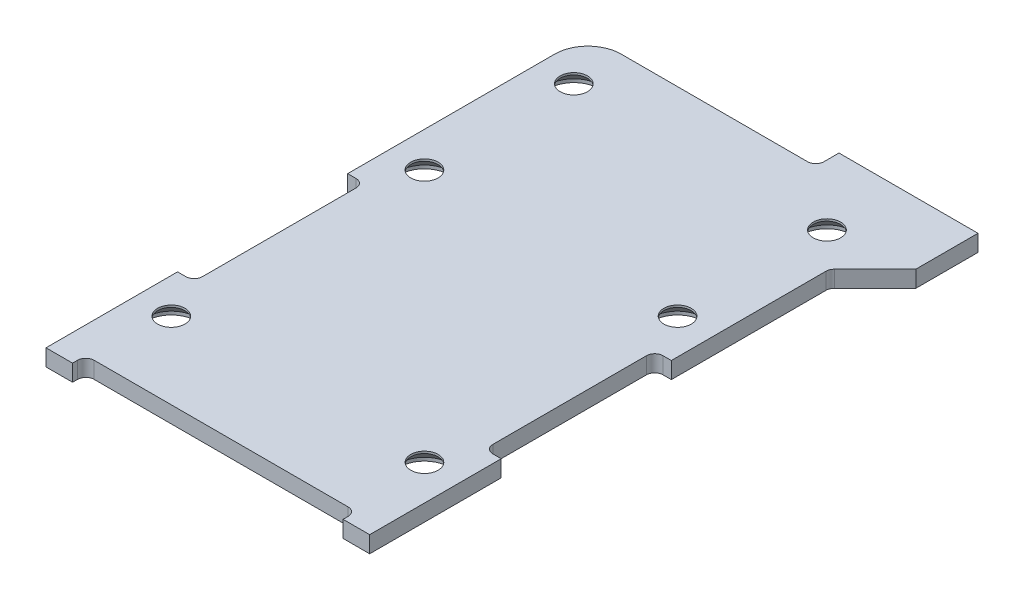
SolidWorks part; units mm, degrees
ref_plane "Front Plane" through (0, 0, 0) normal (0, 0, 1) x (1, 0, 0)
ref_plane "Top Plane" through (0, 0, 0) normal (0, 1, 0) x (1, 0, 0)
ref_plane "Right Plane" through (0, 0, 0) normal (1, 0, 0) x (0, 0, -1)
sketch "Sketch1" plane through (0, 0, 0) normal (0, 1, 0) x (1, 0, 0)
  line L1 (-18, 31.1) -> (18, 31.1)
  line L2 (-18, 31.1) -> (-18, -31.1)
  line L3 (-18, -31.1) -> (18, -31.1)
  line L4 (18, 31.1) -> (18, -31.1)
  line L5 (-18, 31.1) -> (18, -31.1) construction
  line L6 (-18, -31.1) -> (18, 31.1) construction
  point P0 (0, 0)
  dimension "D1" = 36
  dimension "D2" = 62.2
extrude "Base shape" add sketch "Sketch1" along normal blind 2
sketch "Sketch2" plane through (0, 2, 0) normal (0, 1, 0) x (1, 0, 0)
  line L0 (0, 31.1) -> (0, -31.1) construction
  line L1 (18, 31.1) -> (-18, 31.1) construction
  line L2 (-18, -31.1) -> (18, -31.1) construction
  line L4 (-18, 2.15) -> (-17.5, 2.15)
  line L5 (-18, 2.15) -> (-18, -18.35)
  line L6 (-18, -18.35) -> (-17.5, -18.35)
  line L7 (-17.5, 2.15) -> (-17.5, -18.35)
  line L8 (-17.5, -8.1) -> (-18, -8.1) construction
  line L9 (-15.25, -31.1) -> (-15.25, 31.1) construction
  line L11 (-18, -8.1) -> (18, -8.1) construction
  line L13 (15.25, 7.15) -> (15.25, -8.1) construction
  line L14 (15.25, 7.15) -> (0, 7.15) construction
  line L15 (18, -18.35) -> (17.5, -18.35)
  line L16 (17.5, 2.15) -> (17.5, -18.35)
  line L17 (18, 2.15) -> (17.5, 2.15)
  line L18 (18, 2.15) -> (18, -18.35)
  line L19 (18, -31.1) -> (18, 31.1) construction
  line L20 (-18, -31.1) -> (18, -31.1)
  line L21 (-18, -31.1) -> (-18, 14.9)
  line L22 (-18, 14.9) -> (18, 14.9)
  line L23 (18, -31.1) -> (18, 14.9)
  circle A0 centre (15.25, 7.15) radius 1.65
  circle A1 centre (15.25, -23.35) radius 1.65
  circle A2 centre (-15.25, 7.15) radius 1.65
  circle A3 centre (-15.25, -23.35) radius 1.65
  circle A4 centre (-15.25, 25.15) radius 1.65
  circle A5 centre (15.25, 25.15) radius 1.65
  line M13 (18, -31.1) -> (18, 31.1)
  line M15 (-18, 31.1) -> (-18, -31.1)
  dimension "D4" = 3.3
  dimension "D1" = 20.5
  dimension "D2" = 46
  dimension "D3" = 35
  dimension "D5" = 30.5
  dimension "D6" = 18
extrude "Cutouts" cut sketch "Sketch2" against normal up to next contours A2 | A0 | L17 L16 L15 M13 | L7 L4 L6 M15 | A3 | A1 | A4 | A5 region at (-17.75, 2, 8.1) region at (17.75, 2, 8.1) region at (15.25, 2, -7.15) region at (15.25, 2, 23.35) region at (-15.25, 2, -7.15) region at (-15.25, 2, 23.35)
sketch "Sketch3" plane through (0, 0, 0) normal (0, -1, 0) x (1, 0, 0)
  line L0 (18, -16.625) -> (19.5, -16.625) construction
  line L1 (19.5, 32.6) -> (-19.5, 32.6)
  line L2 (19.5, 32.6) -> (19.5, -32.6)
  line L3 (19.5, -32.6) -> (-19.5, -32.6)
  line L4 (-19.5, 32.6) -> (-19.5, -32.6)
  line L5 (19.5, 32.6) -> (-19.5, -32.6) construction
  line L6 (19.5, -32.6) -> (-19.5, 32.6) construction
  line L7 (0, -31.1) -> (0, -32.6) construction
  line L8 (-19.5, -31.1) -> (19.5, -31.1)
  line L9 (-19.5, -2.15) -> (19.5, -2.15)
  line L10 (-19.5, 18.35) -> (19.5, 18.35)
  line L11 (-19.5, 31.1) -> (19.5, 31.1)
  line L12 (-18, 18.35) -> (-17.5, 18.35)
  line L13 (-18, 31.1) -> (-18, 18.35)
  line L14 (18, 31.1) -> (-18, 31.1)
  line L15 (18, 18.35) -> (18, 31.1)
  line L16 (17.5, 18.35) -> (18, 18.35)
  line L17 (17.5, -2.15) -> (17.5, 18.35)
  line L18 (18, -2.15) -> (17.5, -2.15)
  line L19 (18, -31.1) -> (18, -2.15)
  line L20 (-18, -31.1) -> (18, -31.1)
  line L21 (-18, -2.15) -> (-18, -31.1)
  line L22 (-17.5, -2.15) -> (-18, -2.15)
  line L23 (-17.5, 18.35) -> (-17.5, -2.15)
  line L24 (-18, 18.35) -> (-17.5, 18.35)
  line L25 (-18, 31.1) -> (-18, 18.35)
  line L26 (18, 31.1) -> (-18, 31.1)
  line L27 (18, 18.35) -> (18, 31.1)
  line L28 (17.5, 18.35) -> (18, 18.35)
  line L29 (17.5, -2.15) -> (17.5, 18.35)
  line L30 (18, -2.15) -> (17.5, -2.15)
  line L31 (18, -31.1) -> (18, -2.15)
  line L32 (-18, -31.1) -> (18, -31.1)
  line L33 (-18, -2.15) -> (-18, -31.1)
  line L34 (-17.5, -2.15) -> (-18, -2.15)
  line L35 (-17.5, 18.35) -> (-17.5, -2.15)
  line L37 (24.7, -26.4) -> (24.7, -33.9) construction
  line L38 (7.95, -33.9) -> (24.7, -33.9) construction
  line L39 (7.95, -33.9) -> (7.95, -14.9) construction
  line L40 (24.7, -26.4) -> (19.5, -21.2) construction
  line L41 (24.7, -26.4) -> (24.7, -33.9)
  line L42 (7.95, -33.9) -> (24.7, -33.9)
  line L43 (7.95, -33.9) -> (7.95, -14.9)
  line L44 (24.7, -26.4) -> (19.5, -21.2)
  point P2 (0, 0)
  line M15 (18, -31.1) -> (18, -2.15)
  line M16 (18, 31.1) -> (-18, 31.1)
  line M17 (-18, 31.1) -> (-18, 18.35)
  line M35 (-18, -2.15) -> (-18, -31.1)
  line M36 (18, 18.35) -> (18, 31.1)
  dimension "D2" = 1.5
  dimension "D1" = 0
extrude "Extra size" add sketch "Sketch3" against normal up to surface (2 mm away) contours L9 L4 L8 M35 | L9 L8 L2 M15 | L11 L4 L10 M17 | L11 L10 L2 M36 | L4 L11 L2 L1 M16 | L43 L42 L41 L2 L3 | L43 L3 L2 L8 L32 region at (0, 0, 31.85) region at (18.75, 0, 24.725) region at (-18.75, 0, 24.725) region at (18.75, 0, -16.625) region at (-18.75, 0, -16.625) region at (20.0645, 0, -29.7415) region at (13.725, 0, -31.85) up to face at (15.25, 2, 25)
sketch "Sketch4" plane through (0, 0, 0) normal (0, 1, 0) x (1, 0, 0)
  circle A0 centre (-15.25, 25.15) radius 3
  circle A1 centre (15.25, 25.15) radius 3
  circle A2 centre (15.25, 7.15) radius 3
  circle A3 centre (-15.25, 7.15) radius 3
  circle A4 centre (-15.25, -23.35) radius 3
  circle A5 centre (15.25, -23.35) radius 3
  dimension "D1" = 6
extrude "Screw head cut" cut sketch "Sketch4" along normal blind 0.4
chamfer "Screw chamfer" distance 1.35 angle 45 6 edges at (-15.25, 0.4, 25) (15.25, 0.4, 25) (15.25, 0.4, -5.5) (15.25, 0.4, -23.5) (-15.25, 0.4, -23.5) (-15.25, 0.4, -5.5)
fillet "Front fillets" radius 4 1 edges at (-19.5, 1, -31.1)
sketch "Sketch6" plane through (0, 0, 32.6) normal (0, 0, 1) x (1, 0, 0)
  line L0 (19.5, 0) -> (-19.5, 0) construction
  line L1 (19.5, 2) -> (16.3, 2)
  line L2 (19.5, 2) -> (19.5, 0)
  line L3 (19.5, 0) -> (16.3, 0)
  line L4 (16.3, 2) -> (16.3, 0)
  line L7 (-19.5, 0) -> (-16.3, 0)
  line L8 (-19.5, 0) -> (-19.5, 2)
  line L9 (-19.5, 2) -> (-16.3, 2)
  line L10 (-16.3, 0) -> (-16.3, 2)
  line L11 (19.5, 2) -> (-19.5, 2) construction
  line L14 (16.3, 10.2) -> (16.3, 2) construction
  line L15 (-16.3, 2) -> (-16.3, 10.2) construction
extrude "Ledbar sides" add sketch "Sketch6" along normal up to surface (1.6 mm away)
fillet "Milling fillets" radius 1 8 edges at (-16.3, 1, 32.6) (16.3, 1, 32.6) (17.5, 1, -2.15) (17.5, 1, 18.35) (-17.5, 1, -2.15) (-17.5, 1, 18.35) (19.5, 1, -21.2) (7.95, 1, -31.1)
